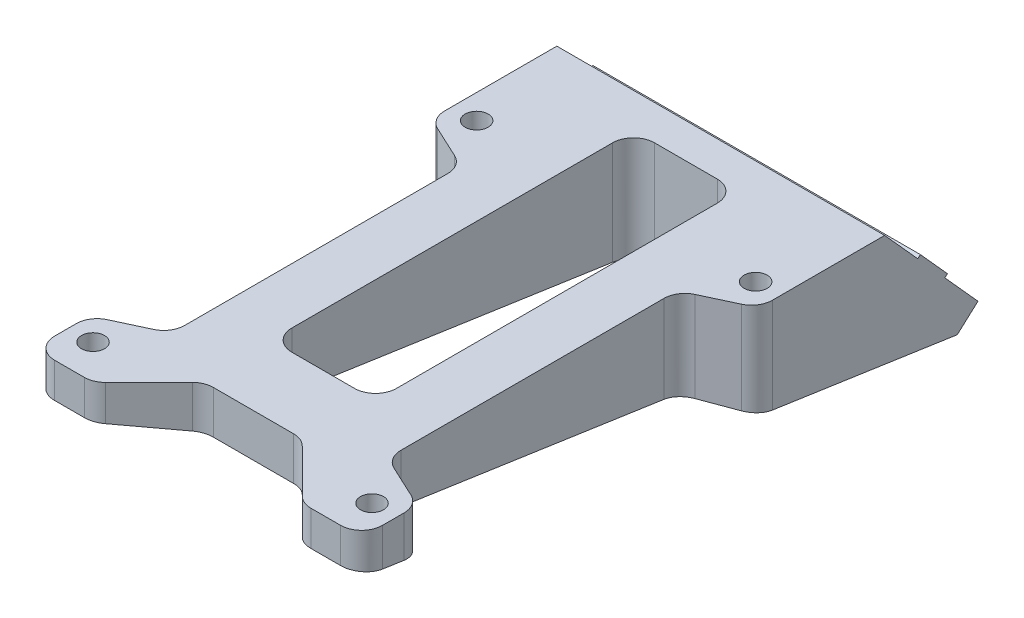
SolidWorks part; units mm, degrees
ref_plane "前视基准面" through (0, 0, 0) normal (0, 0, 1) x (1, 0, 0)
ref_plane "上视基准面" through (0, 0, 0) normal (0, 1, 0) x (1, 0, 0)
ref_plane "右视基准面" through (0, 0, 0) normal (1, 0, 0) x (0, 0, -1)
sketch "草图2" plane through (0, 0, 0) normal (0, 1, 0) x (1, 0, 0)
  line L0 (0, 0) -> (23.5, 0)
  line L1 (23.5, 0) -> (23.5, -14)
  line L4 (23.5, -75) -> (0, -75)
  line L5 (0, -75) -> (0, 0)
  line L6 (23.5, -14) -> (23.5, -75)
  dimension "D1" = 23.5
  dimension "D2" = 75
  dimension "D3" = 23.5
  dimension "D4" = 23.5
  dimension "D6" = 61
extrude "凸台-拉伸2" add sketch "草图2" along normal blind 5
mirror "镜向1" about plane through (0, 5, 75) normal (1, 0, 0) of "凸台-拉伸2"
sketch "草图3" plane through (0, 5, 0) normal (0, 1, 0) x (1, 0, 0)
  line L0 (-41.875, -15) -> (42.0058, -15) construction
  line L1 (-48.5488, -70) -> (45.2773, -70) construction
  line L2 (-20, 7.7517) -> (-20, -80.1072) construction
  line L3 (20, 7.7517) -> (20, -77.5947) construction
  line L4 (-23.5, -75) -> (23.5, -75) construction
  circle A0 centre (-20, -15) radius 1.65
  circle A1 centre (20, -15) radius 1.65
  circle A2 centre (-20, -70) radius 1.65
  circle A3 centre (20, -70) radius 1.65
  point P10 (0, -75)
  dimension "D5" = 3.3
  dimension "D1" = 5
  dimension "D2" = 55
  dimension "D3" = 40
  dimension "D4" = 20
extrude "切除-拉伸1" cut sketch "草图3" against normal through all
sketch "草图5" plane through (0, 0, 0) normal (1, 0, 0) x (0, 0, -1)
  line L0 (-75, 0) -> (10.41, -12.5394)
  line L1 (10.41, -12.5394) -> (13.3826, -9.8629)
  line L2 (13.3826, -9.8629) -> (0, 5)
  line L3 (0, 5) -> (0, 0) construction
  line L4 (-75, 0) -> (0, 0) construction
  line L5 (0, 5) -> (0, 0)
  line L6 (-75, 0) -> (0, 0)
  line L7 (4.7508, -0.2763) -> (8.6318, -4.5866)
  line L8 (4.7508, -0.2763) -> (5.1224, 0.0582)
  line L9 (8.6318, -4.5866) -> (9.0034, -4.252)
  line L10 (5.1224, 0.0582) -> (9.0034, -4.252)
  line L11 (7.0629, -2.0969) -> (3.8382, -5.0004) construction
  dimension "D1" = 20
  dimension "D2" = 4
  dimension "D3" = 42
  dimension "D4" = 10
  dimension "D5" = 5.8
  dimension "D6" = 0.5
extrude "凸台-拉伸3" add sketch "草图5" along normal mid plane 47 contours L6 L0 L1 L2 L7 L5 | L11 L10 L8 L7 | L10 L11 L2 L9 region at (0, -4.2198, 18.1192) region at (0, -3.3417, -7.8473) region at (0, -1.1866, -5.9069)
sketch "草图6" plane through (0, 2.5732, -2.8579) normal (0, 0.6691, -0.7431) x (1, 0, 0)
  line L0 (-23.5, 6.2843) -> (23.5, 6.2843) construction
  line L1 (-23.5, 3.3843) -> (-23.5, 9.1843) construction
  line L2 (23.5, 3.3843) -> (23.5, 9.1843) construction
  line L3 (-13.5, 9.1843) -> (-13.5, 3.3843) construction
  line L4 (23.5, 9.1843) -> (-23.5, 9.1843) construction
  line L5 (23.5, 3.3843) -> (-23.5, 3.3843) construction
  line L6 (13.5, 9.1843) -> (13.5, 3.3843) construction
  line L7 (23.5, 9.1843) -> (-23.5, 9.1843) construction
  line L8 (23.5, 3.3843) -> (-23.5, 3.3843) construction
  circle A0 centre (-13.5, 6.2843) radius 2.6
  circle A1 centre (13.5, 6.2843) radius 2.6
  dimension "D3" = 5.2
  dimension "D1" = 10
  dimension "D2" = 10
extrude "切除-拉伸3" cut sketch "草图6" against normal through all
sketch "草图7" plane through (0, 2.5732, -2.8579) normal (0, 0.6691, -0.7431) x (1, 0, 0)
  circle A0 centre (-13.5, 6.2843) radius 4.5
  circle A1 centre (13.5, 6.2843) radius 4.5
  dimension "D1" = 9
extrude "切除-拉伸4" cut sketch "草图7" against normal up to next from offset 5 offset against normal yes
sketch "草图8" plane through (0, 5, 0) normal (0, -1, 0) x (1, 0, 0)
  circle A0 centre (-20, 15) radius 3
  circle A1 centre (20, 15) radius 3
  circle A2 centre (20, 70) radius 3
  circle A3 centre (-20, 70) radius 3
  dimension "D1" = 6
extrude "切除-拉伸5" cut sketch "草图8" along normal up to next from offset 3
sketch "草图4" plane through (0, 5, 0) normal (0, 1, 0) x (1, 0, 0)
  line L0 (-23.5, -75) -> (23.5, -75) construction
  line L1 (-7.5, -5) -> (7.5, -5)
  line L2 (-7.5, -5) -> (-7.5, -57)
  line L3 (-7.5, -57) -> (7.5, -57)
  line L4 (7.5, -5) -> (7.5, -57)
  line L5 (-15, -75) -> (-7, -67)
  line L6 (-7, -67) -> (7, -67)
  line L7 (7, -67) -> (15, -75)
  line L8 (15, -75) -> (-15, -75)
  line L9 (-23.5, -67) -> (-15.5, -63.2695)
  line L10 (-23.5, -75) -> (-23.5, 0) construction
  line L11 (-15.5, -63.2695) -> (-15.5, -21.7305)
  line L12 (-15.5, -21.7305) -> (-23.5, -18)
  line L13 (-23.5, -18) -> (-23.5, -67)
  line L14 (-23.5, -75) -> (23.5, -75) construction
  line L15 (23.5, 0) -> (-23.5, 0) construction
  line L16 (0, 0) -> (0, -5.79) construction
  line L17 (15.5, -21.7305) -> (23.5, -18)
  line L18 (15.5, -63.2695) -> (15.5, -21.7305)
  line L19 (23.5, -67) -> (15.5, -63.2695)
  line L20 (23.5, -18) -> (23.5, -67)
  point P6 (0, -75)
  point P10 (0, -75)
  dimension "D1" = 18
  dimension "D2" = 52
  dimension "D3" = 15
  dimension "D4" = 7.5
  dimension "D5" = 30
  dimension "D6" = 8
  dimension "D7" = 45
  dimension "D8" = 45
  dimension "D9" = 8
  dimension "D10" = 18
  dimension "D11" = 8
  dimension "D12" = 65
  dimension "D13" = 65
extrude "切除-拉伸2" cut sketch "草图4" against normal through all
fillet "圆角1" radius 3 18 edges at (7.5, -2.6385, 5) (-7.5, -2.6385, 5) (7.5, 1.1787, 57) (-7.5, 1.1787, 57) (23.5, -1.6842, 18) (15.5, -1.4104, 21.7305) (15.5, 1.6389, 63.2695) (23.5, 1.9127, 67) (23.5, 2.5, 75) (15, 2.5, 75) (7, 1.9127, 67) (-7, 1.9127, 67) (-15, 2.5, 75) (-23.5, 2.5, 75) (-23.5, 1.9127, 67) (-15.5, 1.6389, 63.2695) (-15.5, -1.4104, 21.7305) (-23.5, -1.6842, 18)
